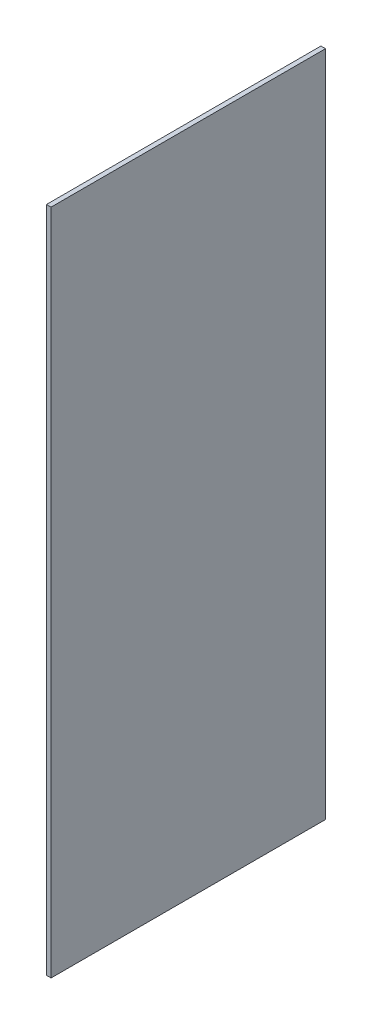
SolidWorks part; units mm, degrees
ref_plane "Front Plane" through (0, 0, 0) normal (0, 0, 1) x (1, 0, 0)
ref_plane "Top Plane" through (0, 0, 0) normal (0, 1, 0) x (1, 0, 0)
ref_plane "Right Plane" through (0, 0, 0) normal (1, 0, 0) x (0, 0, -1)
sketch "Sketch1" plane through (0, 0, 0) normal (1, 0, 0) x (0, 0, -1)
  line L1 (0, 0) -> (-189.738, 0)
  line L2 (0, 0) -> (0, 461.518)
  line L3 (0, 461.518) -> (-189.738, 461.518)
  line L4 (-189.738, 0) -> (-189.738, 461.518)
  dimension "D1" = 461.518
  dimension "D2" = 189.738
extrude "Boss-Extrude1" add sketch "Sketch1" along normal blind 3.175
